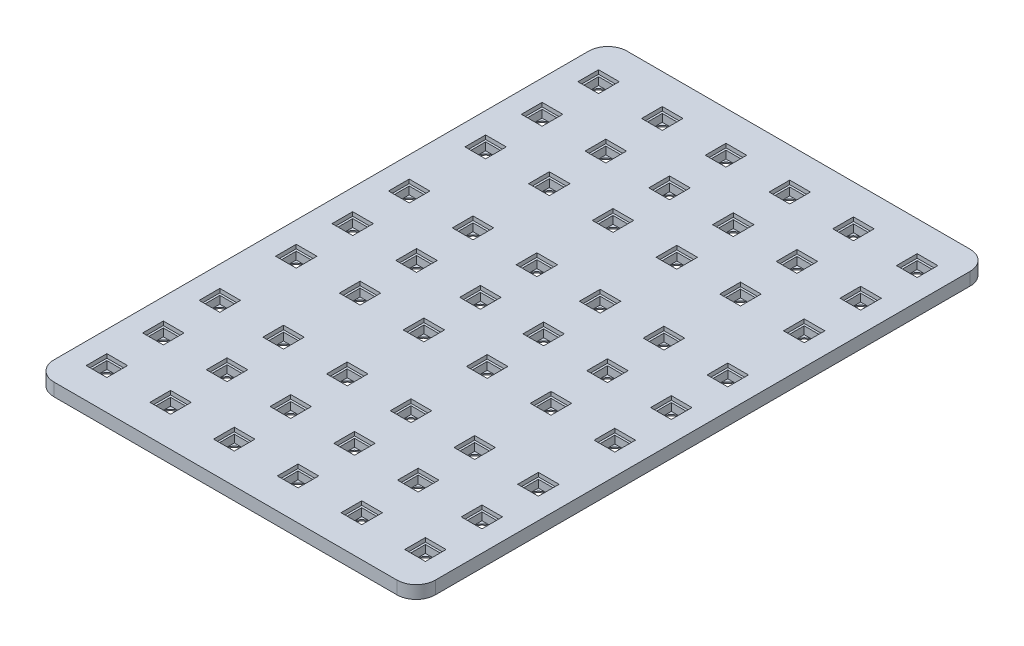
SolidWorks part; units mm, degrees
ref_plane "Front Plane" through (0, 0, 0) normal (0, 0, 1) x (1, 0, 0)
ref_plane "Top Plane" through (0, 0, 0) normal (0, 1, 0) x (1, 0, 0)
ref_plane "Right Plane" through (0, 0, 0) normal (1, 0, 0) x (0, 0, -1)
sketch "Sketch1" plane through (0, 0, 0) normal (0, 1, 0) x (1, 0, 0)
  line L1 (-149.25, -224.25) -> (149.25, -224.25)
  line L2 (-149.25, -224.25) -> (-149.25, 224.25)
  line L3 (-149.25, 224.25) -> (149.25, 224.25)
  line L4 (149.25, -224.25) -> (149.25, 224.25)
  line L5 (-149.25, -224.25) -> (149.25, 224.25) construction
  line L6 (-149.25, 224.25) -> (149.25, -224.25) construction
  point P0 (0, 0)
  dimension "D1" = 448.5
  dimension "D2" = 298.5
extrude "Boss-Extrude1" add sketch "Sketch1" along normal blind 20.1
sketch "Sketch2" plane through (0, 20.1, 0) normal (0, 1, 0) x (1, 0, 0)
  line L0 (-116.25, -176.75) -> (-83.85, -176.75)
  line L1 (-116.25, -176.75) -> (-116.25, -144.35)
  line L2 (-116.25, -144.35) -> (-83.85, -144.35)
  line L3 (-83.85, -176.75) -> (-83.85, -144.35)
  line L4 (-116.25, -176.75) -> (-83.85, -144.35) construction
  line L5 (-116.25, -144.35) -> (-83.85, -176.75) construction
  line L6 (-113.05, -173.55) -> (-87.05, -173.55)
  line L7 (-113.05, -173.55) -> (-113.05, -147.55)
  line L8 (-113.05, -147.55) -> (-87.05, -147.55)
  line L9 (-87.05, -173.55) -> (-87.05, -147.55)
  line L10 (-113.05, -173.55) -> (-87.05, -147.55) construction
  line L11 (-113.05, -147.55) -> (-87.05, -173.55) construction
  line L12 (-16.55, -176.75) -> (15.85, -176.75)
  line L13 (15.85, -176.75) -> (15.85, -144.35)
  line L14 (-16.55, -144.35) -> (15.85, -144.35)
  line L15 (-16.55, -176.75) -> (-16.55, -144.35)
  line L16 (-13.35, -173.55) -> (12.65, -173.55)
  line L17 (12.65, -173.55) -> (12.65, -147.55)
  line L18 (-13.35, -147.55) -> (12.65, -147.55)
  line L19 (-13.35, -173.55) -> (-13.35, -147.55)
  line L20 (83.15, -176.75) -> (115.55, -176.75)
  line L21 (115.55, -176.75) -> (115.55, -144.35)
  line L22 (83.15, -144.35) -> (115.55, -144.35)
  line L23 (83.15, -176.75) -> (83.15, -144.35)
  line L24 (86.35, -173.55) -> (112.35, -173.55)
  line L25 (112.35, -173.55) -> (112.35, -147.55)
  line L26 (86.35, -147.55) -> (112.35, -147.55)
  line L27 (86.35, -173.55) -> (86.35, -147.55)
  line L28 (-16.55, -88.35) -> (15.85, -88.35)
  line L29 (15.85, -88.35) -> (15.85, -55.95)
  line L30 (-16.55, -55.95) -> (15.85, -55.95)
  line L31 (-16.55, -88.35) -> (-16.55, -55.95)
  line L32 (-13.35, -85.15) -> (12.65, -85.15)
  line L33 (12.65, -85.15) -> (12.65, -59.15)
  line L34 (-13.35, -59.15) -> (12.65, -59.15)
  line L35 (-13.35, -85.15) -> (-13.35, -59.15)
  line L36 (83.15, -88.35) -> (115.55, -88.35)
  line L37 (115.55, -88.35) -> (115.55, -55.95)
  line L38 (83.15, -55.95) -> (115.55, -55.95)
  line L39 (83.15, -88.35) -> (83.15, -55.95)
  line L40 (86.35, -85.15) -> (112.35, -85.15)
  line L41 (112.35, -85.15) -> (112.35, -59.15)
  line L42 (86.35, -59.15) -> (112.35, -59.15)
  line L43 (86.35, -85.15) -> (86.35, -59.15)
  line L44 (-16.55, 0.05) -> (15.85, 0.05)
  line L45 (15.85, 0.05) -> (15.85, 32.45)
  line L46 (-16.55, 32.45) -> (15.85, 32.45)
  line L47 (-16.55, 0.05) -> (-16.55, 32.45)
  line L48 (-13.35, 3.25) -> (12.65, 3.25)
  line L49 (12.65, 3.25) -> (12.65, 29.25)
  line L50 (-13.35, 29.25) -> (12.65, 29.25)
  line L51 (-13.35, 3.25) -> (-13.35, 29.25)
  line L52 (83.15, 0.05) -> (115.55, 0.05)
  line L53 (115.55, 0.05) -> (115.55, 32.45)
  line L54 (83.15, 32.45) -> (115.55, 32.45)
  line L55 (83.15, 0.05) -> (83.15, 32.45)
  line L56 (86.35, 3.25) -> (112.35, 3.25)
  line L57 (112.35, 3.25) -> (112.35, 29.25)
  line L58 (86.35, 29.25) -> (112.35, 29.25)
  line L59 (86.35, 3.25) -> (86.35, 29.25)
  line L60 (-116.25, -88.35) -> (-83.85, -88.35)
  line L61 (-83.85, -88.35) -> (-83.85, -55.95)
  line L62 (-116.25, -55.95) -> (-83.85, -55.95)
  line L63 (-116.25, -88.35) -> (-116.25, -55.95)
  line L64 (-113.05, -85.15) -> (-87.05, -85.15)
  line L65 (-87.05, -85.15) -> (-87.05, -59.15)
  line L66 (-113.05, -59.15) -> (-87.05, -59.15)
  line L67 (-113.05, -85.15) -> (-113.05, -59.15)
  line L68 (-116.25, 0.05) -> (-83.85, 0.05)
  line L69 (-83.85, 0.05) -> (-83.85, 32.45)
  line L70 (-116.25, 32.45) -> (-83.85, 32.45)
  line L71 (-116.25, 0.05) -> (-116.25, 32.45)
  line L72 (-113.05, 3.25) -> (-87.05, 3.25)
  line L73 (-87.05, 3.25) -> (-87.05, 29.25)
  line L74 (-113.05, 29.25) -> (-87.05, 29.25)
  line L75 (-113.05, 3.25) -> (-113.05, 29.25)
  line L76 (-149.25, 224.25) -> (-149.25, -224.25) construction
  line L77 (-149.25, -224.25) -> (149.25, -224.25) construction
  line L78 (149.25, 224.25) -> (-149.25, 224.25) construction
  line L79 (-83.85, 240.45) -> (-116.25, 240.45)
  line L80 (-83.85, 240.45) -> (-83.85, 208.05)
  line L81 (-83.85, 208.05) -> (-116.25, 208.05)
  line L82 (-116.25, 240.45) -> (-116.25, 208.05)
  line L83 (-83.85, 240.45) -> (-116.25, 208.05) construction
  line L84 (-83.85, 208.05) -> (-116.25, 240.45) construction
  line L85 (16.05, 240.45) -> (16.05, 208.05)
  line L86 (-87.05, 211.25) -> (-113.05, 211.25)
  line L87 (-87.05, 211.25) -> (-87.05, 237.25)
  line L88 (-87.05, 237.25) -> (-113.05, 237.25)
  line L89 (-113.05, 211.25) -> (-113.05, 237.25)
  line L90 (-87.05, 211.25) -> (-113.05, 237.25) construction
  line L91 (-87.05, 237.25) -> (-113.05, 211.25) construction
  line L92 (16.05, 240.45) -> (-16.35, 240.45)
  line L93 (-16.35, 240.45) -> (-16.35, 208.05)
  line L94 (16.05, 208.05) -> (-16.35, 208.05)
  line L95 (12.85, 211.25) -> (12.85, 237.25)
  line L96 (12.85, 211.25) -> (-13.15, 211.25)
  line L97 (-13.15, 211.25) -> (-13.15, 237.25)
  line L98 (12.85, 237.25) -> (-13.15, 237.25)
  line L99 (115.95, 240.45) -> (115.95, 208.05)
  line L100 (115.95, 240.45) -> (83.55, 240.45)
  line L101 (83.55, 240.45) -> (83.55, 208.05)
  line L102 (115.95, 208.05) -> (83.55, 208.05)
  line L103 (112.75, 211.25) -> (112.75, 237.25)
  line L104 (112.75, 211.25) -> (86.75, 211.25)
  line L105 (86.75, 211.25) -> (86.75, 237.25)
  line L106 (112.75, 237.25) -> (86.75, 237.25)
  line L107 (16.05, 152.05) -> (16.05, 119.65)
  line L108 (16.05, 152.05) -> (-16.35, 152.05)
  line L109 (-16.35, 152.05) -> (-16.35, 119.65)
  line L110 (16.05, 119.65) -> (-16.35, 119.65)
  line L111 (12.85, 122.85) -> (12.85, 148.85)
  line L112 (12.85, 122.85) -> (-13.15, 122.85)
  line L113 (-13.15, 122.85) -> (-13.15, 148.85)
  line L114 (12.85, 148.85) -> (-13.15, 148.85)
  line L115 (115.95, 152.05) -> (115.95, 119.65)
  line L116 (115.95, 152.05) -> (83.55, 152.05)
  line L117 (83.55, 152.05) -> (83.55, 119.65)
  line L118 (115.95, 119.65) -> (83.55, 119.65)
  line L119 (112.75, 122.85) -> (112.75, 148.85)
  line L120 (112.75, 122.85) -> (86.75, 122.85)
  line L121 (86.75, 122.85) -> (86.75, 148.85)
  line L122 (112.75, 148.85) -> (86.75, 148.85)
  line L123 (-83.85, 152.05) -> (-83.85, 119.65)
  line L124 (-83.85, 152.05) -> (-116.25, 152.05)
  line L125 (-116.25, 152.05) -> (-116.25, 119.65)
  line L126 (-83.85, 119.65) -> (-116.25, 119.65)
  line L127 (-87.05, 122.85) -> (-87.05, 148.85)
  line L128 (-87.05, 122.85) -> (-113.05, 122.85)
  line L129 (-113.05, 122.85) -> (-113.05, 148.85)
  line L130 (-87.05, 148.85) -> (-113.05, 148.85)
  circle A0 centre (-100.05, -160.55) radius 12.5
  circle A1 centre (-0.35, -160.55) radius 12.5
  circle A2 centre (99.35, -160.55) radius 12.5
  circle A3 centre (-0.35, -72.15) radius 12.5
  circle A4 centre (99.35, -72.15) radius 12.5
  circle A5 centre (-0.35, 16.25) radius 12.5
  circle A6 centre (99.35, 16.25) radius 12.5
  circle A7 centre (-100.05, -72.15) radius 12.5
  circle A8 centre (-100.05, 16.25) radius 12.5
  circle A9 centre (-100.05, 224.25) radius 12.5
  circle A10 centre (-0.15, 224.25) radius 12.5
  circle A11 centre (99.75, 224.25) radius 12.5
  circle A12 centre (-0.15, 135.85) radius 12.5
  circle A13 centre (99.75, 135.85) radius 12.5
  circle A14 centre (-100.05, 135.85) radius 12.5
  point P0 (-100.05, -160.55)
  point P6 (-100.05, -160.55)
  point P96 (-100.05, 224.25)
  point P103 (-100.05, 224.25)
  line M11 (149.25, 224.25) -> (-149.25, 224.25)
  dimension "D1" = 25
  dimension "D2" = 26
  dimension "D3" = 32.4
  dimension "D6" = 33
  dimension "D7" = 47.5
  dimension "D4" = 3
  dimension "D5" = 3
  dimension "D8" = 3
  dimension "D9" = 2
extrude "Cut-Extrude1" cut sketch "Sketch2" against normal blind 6.2 contours L0 L3 L2 L1 L9 L6 L7 L8 | L15 L12 L13 L14 L16 L19 L18 L17 | L23 L20 L21 L22 L24 L27 L26 L25 | L39 L36 L37 L38 L40 L43 L42 L41 | L31 L28 L29 L30 L32 L35 L34 L33 | L63 L60 L61 L62 L64 L67 L66 L65 | L71 L68 L69 L70 L72 L75 L74 L73 | L47 L44 L45 L46 L48 L51 L50 L49 | L55 L52 L53 L54 L56 L59 L58 L57 | L118 L115 L116 L117 L122 L119 L120 L121 | L110 L107 L108 L109 L114 L111 L112 L113 | L126 L123 L124 L125 L130 L127 L128 L129 | L86 L89 L82 L81 L80 L87 M11 | L96 L97 L93 L94 L85 L95 M11 | L104 L105 L101 L102 L99 L103 M11 region at (-115.7918, 20.1, 160.55) region at (-16.0918, 20.1, 160.55) region at (83.6082, 20.1, 160.55) region at (-16.0918, 20.1, 72.15) region at (83.6082, 20.1, 72.15) region at (-16.0918, 20.1, -16.25) region at (83.6082, 20.1, -16.25) region at (-115.7918, 20.1, 72.15) region at (-115.7918, 20.1, -16.25) region at (85.15, 20.1, -223.8878) region at (-14.75, 20.1, -223.8878) region at (-84.2122, 20.1, -216.15) region at (15.5918, 20.1, -135.85) region at (115.4918, 20.1, -135.85) region at (-84.3082, 20.1, -135.85)
extrude "Cut-Extrude2" cut sketch "Sketch2<3>" against normal blind 18.2 contours L6 L9 L8 L7 A0 | L19 L16 L17 L18 A1 | L27 L24 L25 L26 A2 | L43 L40 L41 L42 A4 | L35 L32 L33 L34 A3 | L67 L64 L65 L66 A7 | L127 L130 L129 L128 A14 | A9 L89 L86 L87 M11 | A10 L97 L96 L95 M11 | L111 L114 L113 L112 A12 | L119 L122 L121 L120 A13 | A11 L105 L104 L103 M11 | L59 L56 L57 L58 A6 | L51 L48 L49 L50 A5 | L75 L72 L73 L74 A8 region at (-112.6823, 20.1, 160.55) region at (-12.9823, 20.1, 160.55) region at (86.7177, 20.1, 160.55) region at (-12.9823, 20.1, 72.15) region at (86.7177, 20.1, 72.15) region at (-12.9823, 20.1, -16.25) region at (86.7177, 20.1, -16.25) region at (-112.6823, 20.1, 72.15) region at (-112.6823, 20.1, -16.25) region at (-87.3407, 20.1, -217.75) region at (-12.9, 20.1, -223.9593) region at (87, 20.1, -223.9593) region at (-0.15, 20.1, -123.2177) region at (99.75, 20.1, -123.2177) region at (-100.05, 20.1, -123.2177)
sketch "Sketch2<3>" plane through (0, 20.1, 0) normal (0, 1, 0) x (1, 0, 0) same geometry as "Sketch2"
extrude "Cut-Extrude3" cut sketch "Sketch2<4>" against normal through all contours A0 | A1 | A2 | A4 | A3 | A7 | A8 | A5 | A6 | A13 | A12 | A14 | A9 M11 | A10 M11 | A11 M11 region at (-100.05, 20.1, -218.9448) region at (-0.15, 20.1, -218.9448) region at (99.75, 20.1, -218.9448) region at (-100.05, 20.1, 160.55) region at (-0.35, 20.1, 160.55) region at (99.35, 20.1, 160.55) region at (-0.35, 20.1, 72.15) region at (99.35, 20.1, 72.15) region at (-0.35, 20.1, -16.25) region at (99.35, 20.1, -16.25) region at (-100.05, 20.1, 72.15) region at (-100.05, 20.1, -16.25) region at (-0.15, 20.1, -135.85) region at (99.75, 20.1, -135.85) region at (-100.05, 20.1, -135.85)
sketch "Sketch2<4>" plane through (0, 20.1, 0) normal (0, 1, 0) x (1, 0, 0) same geometry as "Sketch2"
fillet "Fillet1" radius 30 1 edges at (-149.25, 10.05, 224.25)
mirror "Mirror1" about plane through (149.25, 20.1, 224.25) normal (-1, 0, 0) of bodies 105
mirror "Mirror2" about plane through (-149.25, 20.1, -224.25) normal (0, 0, 1) of bodies 106
shell "Shell1" thickness 2 removed face at (-100.05, 0, -211.75)
